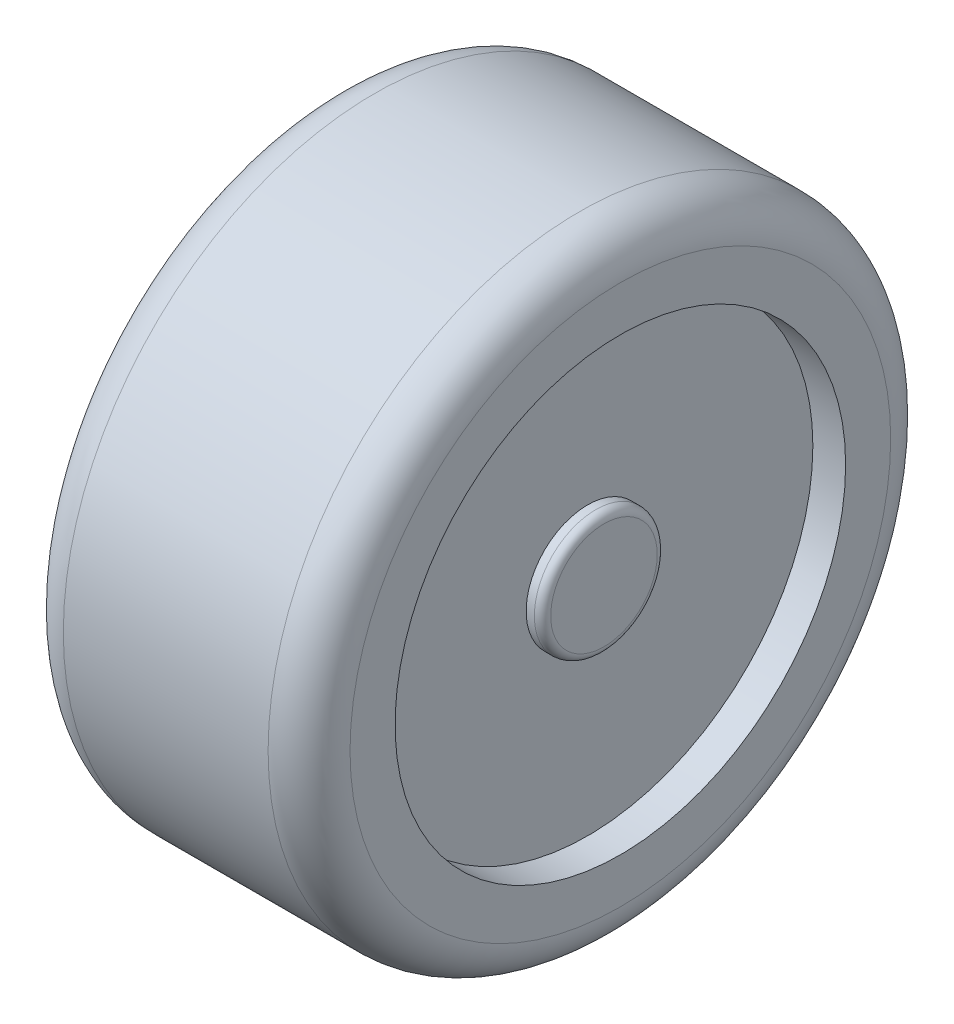
SolidWorks part; units mm, degrees
ref_plane "Front Plane" through (0, 0, 0) normal (0, 0, 1) x (1, 0, 0)
ref_plane "Top Plane" through (0, 0, 0) normal (0, 1, 0) x (1, 0, 0)
ref_plane "Right Plane" through (0, 0, 0) normal (1, 0, 0) x (0, 0, -1)
sketch "Sketch1" plane through (0, 0, 0) normal (1, 0, 0) x (0, 0, -1)
  circle A0 centre (0, 0) radius 38
  circle A1 centre (0, 0) radius 27.5
  circle A2 centre (0, 0) radius 7.5
  circle A3 centre (0, 0) radius 3.5
  dimension "D1" = 76
  dimension "D2" = 7
  dimension "D3" = 15
  dimension "D4" = 55
extrude "Boss-Extrude1" add sketch "Sketch1" against normal blind 30 and the other way blind 5 contours A0 A1 region at (0, 0, 36.9252)
extrude "Boss-Extrude2" add sketch "Sketch1<3>" against normal blind 7 and the other way blind 3 separate body contours A2 A3 | A3 region at (0, 0, 7.2879)
sketch "Sketch1<3>" plane through (0, 0, 0) normal (1, 0, 0) x (0, 0, -1) same geometry as "Sketch1"
extrude "Boss-Extrude3" add sketch "Sketch1<4>" against normal blind 50 contours A3
sketch "Sketch1<4>" plane through (0, 0, 0) normal (1, 0, 0) x (0, 0, -1) same geometry as "Sketch1"
extrude "Boss-Extrude4" add sketch "Sketch1<5>" along normal mid plane 2 contours A1 A2 region at (0, 0, 26.7222)
sketch "Sketch1<5>" plane through (0, 0, 0) normal (1, 0, 0) x (0, 0, -1) same geometry as "Sketch1"
fillet "Fillet1" radius 5 2 edges at (-30, 0, -38) (5, 0, -38)
fillet "Fillet2" radius 1 1 edges at (3, 0, -7.5)
